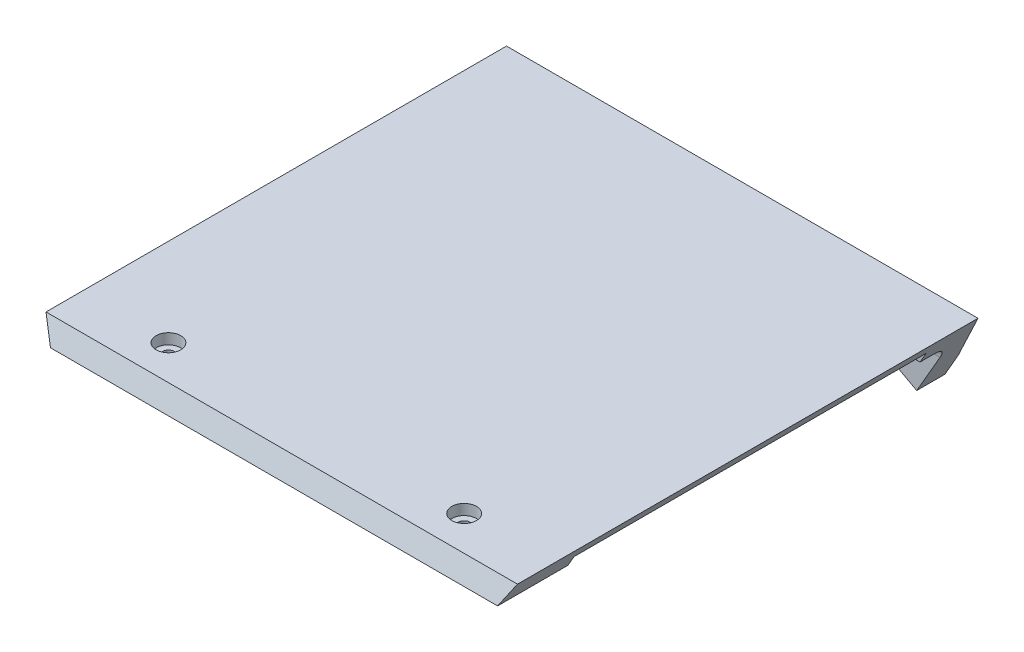
SolidWorks part; units mm, degrees
ref_plane "Front Plane" through (0, 0, 0) normal (0, 0, 1) x (1, 0, 0)
ref_plane "Top Plane" through (0, 0, 0) normal (0, 1, 0) x (1, 0, 0)
ref_plane "Right Plane" through (0, 0, 0) normal (1, 0, 0) x (0, 0, -1)
sketch "Sketch1" plane through (0, 0, 0) normal (0, 1, 0) x (1, 0, 0)
  line L0 (0, 64) -> (0, -64) construction
  line L1 (-63.5, 64) -> (63.5, 64)
  line L2 (-63.5, 64) -> (-63.5, -64)
  line L3 (-63.5, -64) -> (63.5, -64)
  line L4 (63.5, 64) -> (63.5, -64)
  line L5 (-63.5, 64) -> (63.5, -64) construction
  line L6 (-63.5, -64) -> (63.5, 64) construction
  circle A0 centre (-42, -52) radius 1.7
  circle A1 centre (42, -52) radius 1.7
  point P0 (0, 0)
  dimension "D7" = 3.4
  dimension "D8" = 3.4
  dimension "D1" = 127
  dimension "D2" = 12
  dimension "D3" = 12
  dimension "D4" = 42
  dimension "D5" = 42
  dimension "D6" = 128
extrude "Boss-Extrude2" add sketch "Sketch1" along normal blind 6
sketch "Sketch2" plane through (0, 0, -64) normal (0, 0, -1) x (-1, 0, 0)
  line L0 (0, 0) -> (0, -111) construction
  line L1 (-63.5, 6) -> (-63.5, -21.1793)
  line L2 (63.5, 6) -> (63.5, -21.1793)
  line L4 (63.5, 6) -> (-63.5, 6)
  arc A1 (63.5, -21.1793) -> (-63.5, -21.1793) centre (0, -111) ccw
  dimension "D2" = 220
extrude "Boss-Extrude3" add sketch "Sketch2" along normal blind 8
sketch "Sketch3" plane through (0, 6, 0) normal (0, 1, 0) x (1, 0, 0)
  circle A0 centre (42, -52) radius 3.5
  circle A1 centre (-42, -52) radius 3.5
  dimension "D1" = 7
  dimension "D2" = 7
extrude "Cut-Extrude1" cut sketch "Sketch3" against normal blind 3
fillet "Chamfer1" radius 3 1 edges at (0, 6, -72)
draft "Draft2" type of draft neutral plane draft angle 30 neutral plane "Top Plane" faces to draft 1 face at (-63.5, -5.6227, -30.4286) neutral plane through (0, 0, 0) neutral plane normal (0, 1, 0) reverse direction yes parameters "D1"=30
draft "Draft3" type of draft neutral plane draft angle 30 neutral plane "Top Plane" faces to draft 1 face at (63.5, -5.6227, -30.4286) neutral plane through (0, 0, 0) neutral plane normal (0, 1, 0) reverse direction yes parameters "D1"=30
fillet "Fillet5" radius 4 1 edges at (0, 0, -64)
draft "Draft4" type of draft neutral plane draft angle 20 neutral plane "Top Plane" faces to draft 1 face at (0, 3, 64) neutral plane through (0, 0, 0) neutral plane normal (0, 1, 0) parameters "D1"=20
sketch "Sketch4" plane through (0, 0, 0) normal (0, -1, 0) x (1, 0, 0)
  line L8 (-63.5, 64) -> (63.5, 64) construction
  line L9 (-83.5, 44) -> (83.5, 44)
  line L10 (-83.5, 44) -> (-83.5, -56)
  line L11 (-83.5, -56) -> (83.5, -56)
  line L12 (83.5, 44) -> (83.5, -56)
  line L13 (-63.5, -60) -> (-25.5147, -60) construction
  line L14 (-63.5, -60) -> (-63.5, 64) construction
  line L15 (63.5, 64) -> (63.5, -60) construction
  dimension "D1" = 20
  dimension "D2" = 4
  dimension "D3" = 20
  dimension "D4" = 20
extrude "Cut-Extrude2" cut sketch "Sketch4" against normal blind 3
